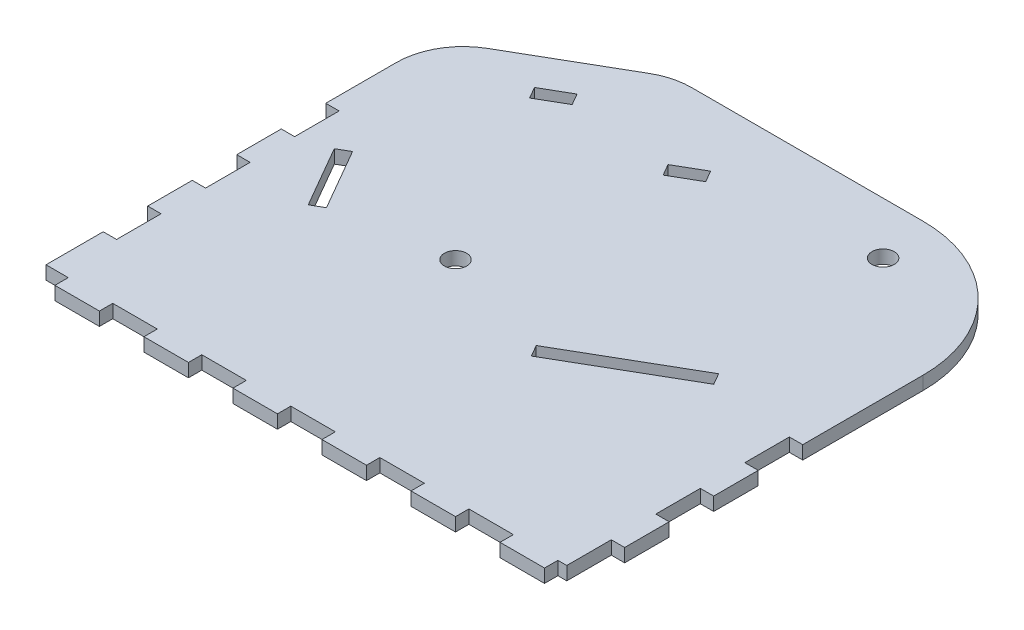
SolidWorks part; units mm, degrees
ref_plane "Alzado" through (0, 0, 0) normal (0, 0, 1) x (1, 0, 0)
ref_plane "Planta" through (0, 0, 0) normal (0, 1, 0) x (1, 0, 0)
ref_plane "Vista lateral" through (0, 0, 0) normal (1, 0, 0) x (0, 0, -1)
sketch "Croquis1" plane through (0, 0, 0) normal (0, 1, 0) x (1, 0, 0)
  line L0 (0, 0) -> (120, 0) construction
  line L1 (0, 0) -> (45, 0)
  line L2 (45, 0) -> (45, 50) construction
  line L3 (45, 0) -> (92.72, 0)
  line L4 (92.72, 0) -> (92.72, 98.34) construction
  line L5 (0, 0) -> (0, 81.7078) construction
  line L6 (38.0227, 110) -> (90, 110)
  line L7 (120, 110) -> (120, 0) construction
  line L8 (0, 0) -> (0, 62.3) construction
  line L9 (0, 62.3) -> (7.3, 62.3) construction
  line L10 (7.3, 62.3) -> (20.3, 39.7833) construction
  line L11 (7.3, 62.3) -> (9.8981, 63.8) construction
  line L12 (20.3, 39.7833) -> (22.8981, 41.2833) construction
  line L13 (22.8981, 41.2833) -> (9.8981, 63.8) construction
  line L14 (16.3981, 52.5417) -> (12.3981, 59.4699)
  line L15 (12.3981, 59.4699) -> (9.8, 57.9699)
  line L16 (12.3981, 59.4699) -> (20.3981, 45.6135)
  line L17 (20.3981, 45.6135) -> (17.8, 44.1135)
  line L18 (9.8, 57.9699) -> (17.8, 44.1135)
  line L19 (0, 0) -> (56.92, 0)
  line L20 (56.92, 0) -> (56.92, 34.36) construction
  line L21 (56.92, 34.36) -> (110.6136, 65.36) construction
  line L22 (56.92, 34.36) -> (58.42, 31.7619) construction
  line L23 (58.42, 31.7619) -> (112.1136, 62.7619) construction
  line L24 (112.1136, 62.7619) -> (110.6136, 65.36) construction
  line L25 (83.7668, 49.86) -> (70.7764, 42.36)
  line L26 (70.7764, 42.36) -> (72.2764, 39.7619)
  line L27 (72.2764, 39.7619) -> (85.2668, 47.2619)
  line L28 (85.2668, 47.2619) -> (83.7668, 49.86) construction
  line L29 (96.7572, 57.36) -> (98.2572, 54.7619)
  line L30 (83.7668, 49.86) -> (96.7572, 57.36)
  line L31 (85.2668, 47.2619) -> (98.2572, 54.7619)
  line L32 (0, 110) -> (18.41, 110) construction
  line L33 (18.41, 110) -> (18.41, 87.77) construction
  line L34 (18.41, 87.77) -> (31.4004, 95.27) construction
  line L35 (31.4004, 95.27) -> (29.9004, 97.8681) construction
  line L36 (18.41, 87.77) -> (16.91, 90.3681) construction
  line L37 (29.9004, 97.8681) -> (16.91, 90.3681) construction
  line L38 (24.9052, 91.52) -> (23.4052, 94.1181) construction
  line L39 (23.4052, 94.1181) -> (26.4363, 95.8681)
  line L40 (26.4363, 95.8681) -> (27.9363, 93.27)
  line L41 (27.9363, 93.27) -> (24.9052, 91.52)
  line L42 (20.3741, 92.3681) -> (21.8741, 89.77)
  line L43 (23.4052, 94.1181) -> (20.3741, 92.3681)
  line L44 (24.9052, 91.52) -> (21.8741, 89.77)
  line L45 (23.4052, 94.1181) -> (20.3741, 92.3681)
  line L46 (24.9052, 91.52) -> (21.8741, 89.77)
  line L47 (0, 110) -> (48.41, 110) construction
  line L48 (48.41, 110) -> (48.41, 87.77) construction
  line L49 (56.4363, 95.8681) -> (57.9363, 93.27)
  line L50 (48.41, 87.77) -> (61.4004, 95.27) construction
  line L51 (54.9052, 91.52) -> (51.8741, 89.77)
  line L52 (53.4052, 94.1181) -> (50.3741, 92.3681)
  line L53 (61.4004, 95.27) -> (59.9004, 97.8681) construction
  line L54 (57.9363, 93.27) -> (54.9052, 91.52)
  line L55 (48.41, 87.77) -> (46.91, 90.3681) construction
  line L56 (54.9052, 91.52) -> (51.8741, 89.77)
  line L57 (50.3741, 92.3681) -> (51.8741, 89.77)
  line L58 (59.9004, 97.8681) -> (46.91, 90.3681) construction
  line L59 (53.4052, 94.1181) -> (56.4363, 95.8681)
  line L60 (48.41, 110) -> (48.41, 87.77) construction
  line L61 (53.4052, 94.1181) -> (50.3741, 92.3681)
  line L62 (54.9052, 91.52) -> (53.4052, 94.1181) construction
  line L63 (60, 0) -> (60, 3)
  line L64 (65, 3) -> (55, 3)
  line L65 (55, 3) -> (55, 0)
  line L66 (55, 0) -> (45, 0)
  line L67 (45, 0) -> (45, 3)
  line L68 (45, 3) -> (35, 3)
  line L69 (35, 3) -> (35, 0)
  line L70 (35, 0) -> (25, 0)
  line L71 (25, 0) -> (25, 3)
  line L72 (25, 3) -> (15, 3)
  line L73 (15, 3) -> (15, 0)
  line L74 (15, 0) -> (5, 0)
  line L75 (5, 0) -> (5, 3)
  line L76 (5, 3) -> (0, 3)
  line L77 (115, 3) -> (120, 3) construction
  line L78 (115, 0) -> (115, 3)
  line L79 (105, 3) -> (105, 0)
  line L80 (95, 3) -> (105, 3)
  line L81 (95, 0) -> (95, 3)
  line L82 (85, 3) -> (85, 0)
  line L83 (75, 3) -> (85, 3)
  line L84 (75, 0) -> (75, 3)
  line L85 (65, 3) -> (65, 0)
  line L86 (5, 0) -> (15, 0)
  line L87 (25, 0) -> (35, 0)
  line L88 (45, 0) -> (55, 0)
  line L89 (65, 0) -> (75, 0)
  line L90 (85, 0) -> (95, 0)
  line L91 (105, 0) -> (115, 0)
  line L92 (7.5, 94.6982) -> (30.5227, 107.9904)
  line L93 (0, 40.8539) -> (3, 40.8539)
  line L94 (3, 45.8539) -> (3, 35.8539)
  line L95 (3, 35.8539) -> (0, 35.8539)
  line L96 (0, 35.8539) -> (0, 25.8539)
  line L97 (0, 25.8539) -> (3, 25.8539)
  line L98 (3, 25.8539) -> (3, 15.8539)
  line L99 (3, 15.8539) -> (0, 15.8539)
  line L100 (3, 65.8539) -> (0, 65.8539)
  line L101 (3, 55.8539) -> (3, 65.8539)
  line L102 (0, 55.8539) -> (3, 55.8539)
  line L103 (3, 45.8539) -> (0, 45.8539)
  line L104 (0, 81.7078) -> (0, 65.8539)
  line L105 (0, 55.8539) -> (0, 45.8539)
  line L106 (0, 35.8539) -> (0, 25.8539)
  line L107 (0, 15.8539) -> (0, 3)
  line L108 (120, 3) -> (120, 53) construction
  line L109 (120, 3) -> (120, 28) construction
  line L110 (120, 28) -> (117, 28) construction
  line L111 (117, 33) -> (117, 23)
  line L112 (117, 23) -> (120, 23)
  line L113 (120, 23) -> (120, 13) construction
  line L114 (120, 13) -> (117, 13)
  line L115 (117, 13) -> (117, 3)
  line L116 (117, 43) -> (117, 53)
  line L117 (120, 43) -> (117, 43)
  line L118 (117, 33) -> (120, 33)
  line L119 (117, 53) -> (120, 53)
  line L120 (115, 3) -> (117, 3)
  line L121 (120, 80) -> (120, 53)
  line L122 (120, 43) -> (120, 33)
  line L123 (120, 23) -> (120, 13)
  circle A0 centre (45, 50) radius 2.5
  circle A1 centre (92.72, 98.34) radius 2.5
  arc A2 (7.5, 94.6982) -> (0, 81.7078) centre (15, 81.7078) ccw
  arc A3 (38.0227, 110) -> (30.5227, 107.9904) centre (38.0227, 95) ccw
  arc A4 (120, 80) -> (90, 110) centre (90, 80) ccw
  dimension "D3" = 5
  dimension "D6" = 5
  dimension "D7" = 15
  dimension "D24" = 15
  dimension "D59" = 30
  dimension "D1" = 120
  dimension "D2" = 45
  dimension "D4" = 47.72
  dimension "D5" = 98.34
  dimension "D8" = 62.3
  dimension "D9" = 7.3
  dimension "D10" = 120
  dimension "D11" = 26
  dimension "D12" = 90
  dimension "D13" = 3
  dimension "D14" = 3
  dimension "D15" = 90
  dimension "D16" = 8
  dimension "D17" = 56.92
  dimension "D18" = 34.36
  dimension "D19" = 120
  dimension "D20" = 90
  dimension "D21" = 3
  dimension "D22" = 62
  dimension "D23" = 15
  dimension "D25" = 22.23
  dimension "D26" = 60
  dimension "D27" = 15
  dimension "D28" = 90
  dimension "D29" = 90
  dimension "D30" = 3
  dimension "D31" = 3
  dimension "D32" = 3.5
  dimension "D33" = 50
  dimension "D34" = 22.23
  dimension "D35" = 60
  dimension "D36" = 15
  dimension "D37" = 90
  dimension "D38" = 90
  dimension "D39" = 3
  dimension "D40" = 3
  dimension "D41" = 3.5
  dimension "D42" = 3
  dimension "D43" = 5
  dimension "D44" = 10
  dimension "D45" = 10
  dimension "D46" = 10
  dimension "D47" = 10
  dimension "D48" = 10
  dimension "D49" = 120
  dimension "D50" = 3
  dimension "D51" = 5
  dimension "D52" = 10
  dimension "D53" = 10
  dimension "D54" = 50
  dimension "D55" = 25
  dimension "D56" = 3
  dimension "D57" = 5
  dimension "D58" = 10
extrude "Saliente-Extruir1" add sketch "Croquis1" along normal blind 3 contours L7 L6 L5 L0 L3 A1 A0 L31 L27 L26 L25 L30 L29 L18 L15 L14 L16 L17 L41 L44 L42 L43 L39 L40 L52 L59 L49 L54 L51 L57 region at (60.5934, 0, -53.8188)
